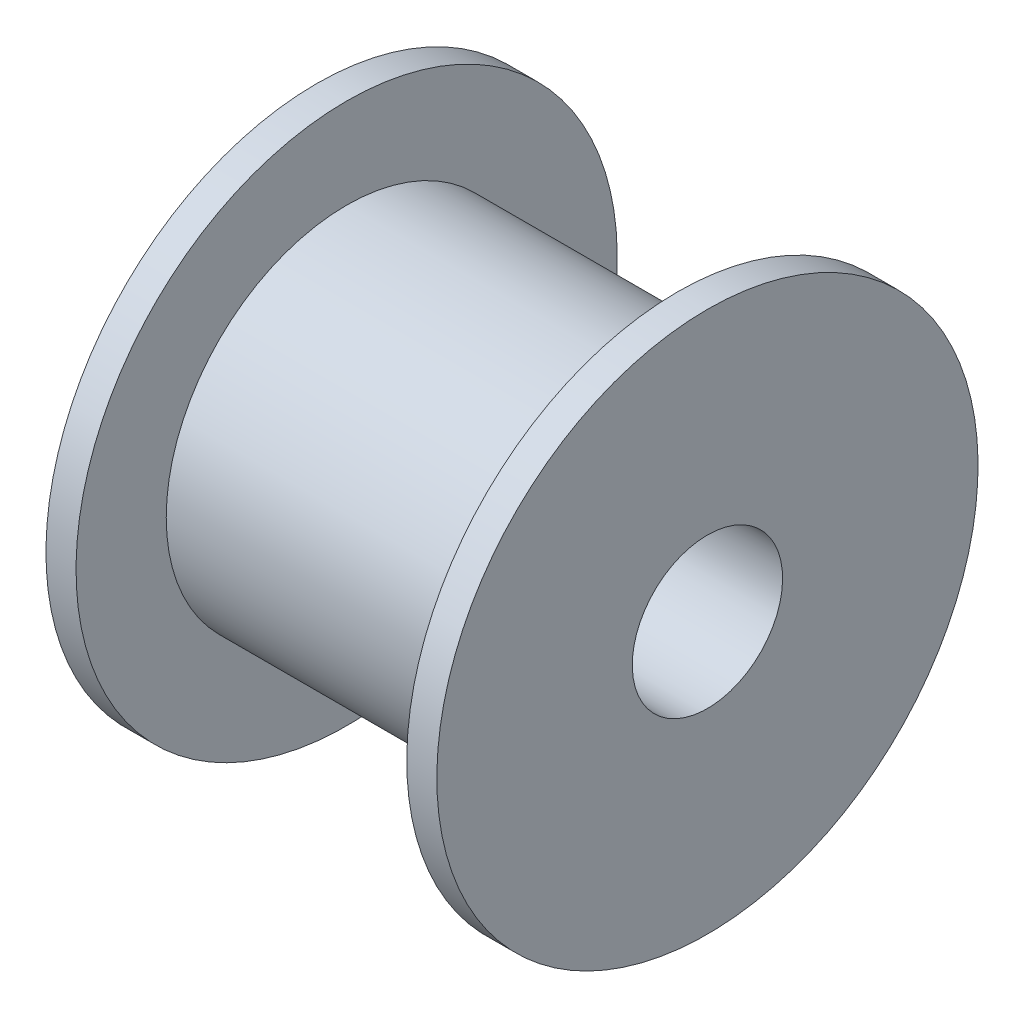
SolidWorks part; units mm, degrees
ref_plane "Front" through (0, 0, 0) normal (0, 0, 1) x (1, 0, 0)
ref_plane "Top" through (0, 0, 0) normal (0, 1, 0) x (1, 0, 0)
ref_plane "Right" through (0, 0, 0) normal (1, 0, 0) x (0, 0, -1)
sketch "Эскиз2" plane through (0, 0, 0) normal (0, 0, 1) x (1, 0, 0)
  line L0 (0, 0) -> (-13, 0)
  line L1 (-13, 0) -> (-13, 9)
  line L2 (-13, 9) -> (-12, 9)
  line L3 (0, 9) -> (0, 0)
  line L4 (-13, 9) -> (-12, 9)
  line L5 (-12, 9) -> (-12, 6)
  line L6 (-12, 6) -> (-1, 6)
  line L7 (-1, 6) -> (-1, 9)
  line L8 (-1, 9) -> (0, 9)
  line L9 (-13, 2.5) -> (0, 2.5)
revolve "Повернуть1" add sketch "Эскиз2" angle 360 about L0 region at (-6.5, 4.6286, 0)
